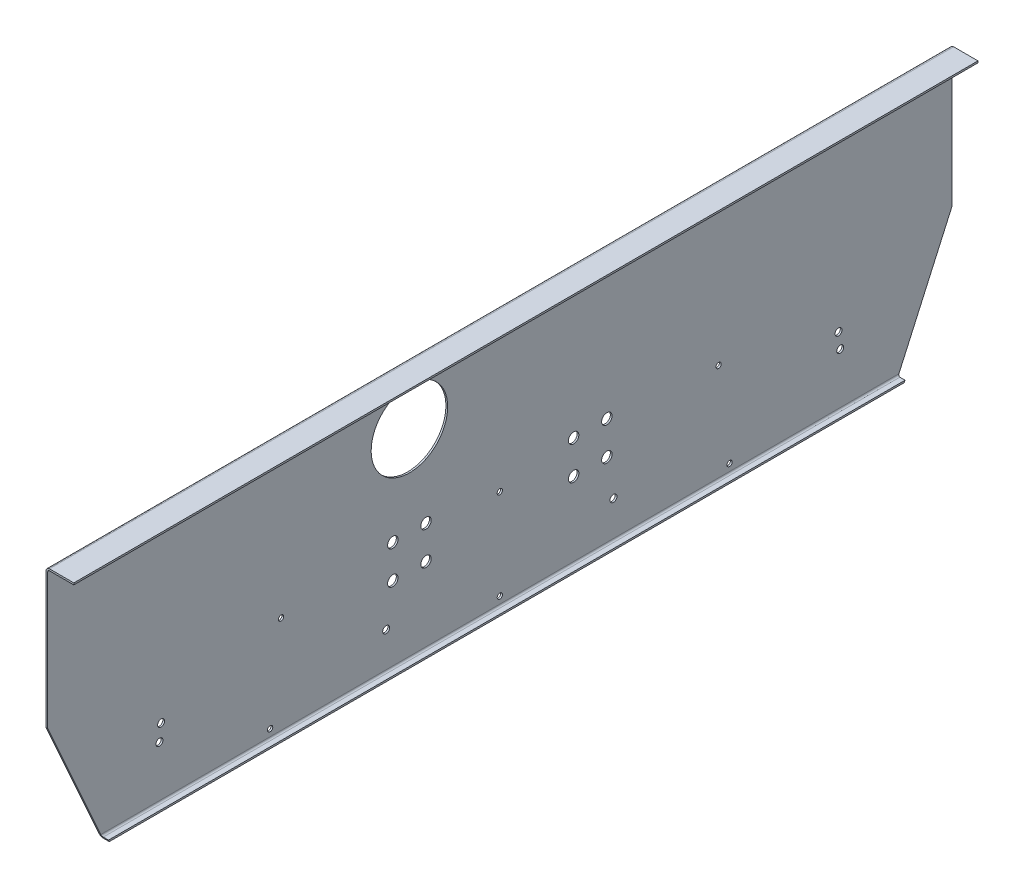
SolidWorks part; units mm, degrees
material "6061-T6 (SS)"
ref_plane "Front Plane" through (0, 0, 0) normal (0, 0, 1) x (1, 0, 0)
ref_plane "Top Plane" through (0, 0, 0) normal (0, 1, 0) x (1, 0, 0)
ref_plane "Right Plane" through (0, 0, 0) normal (1, 0, 0) x (0, 0, -1)
sketch "Sketch3" plane through (0, 0, 0) normal (0, 0, 1) x (1, 0, 0)
  line L0 (3.175, 233.4895) -> (25.4, 233.4895)
  line L1 (0, 231.902) -> (0, 0)
  line L4 (1.5875, 0) -> (1.5875, 231.902)
  line L5 (25.4, 233.4895) -> (25.4, 235.077)
  line L6 (25.4, 235.077) -> (3.175, 235.077)
  line L7 (0, 115.951) -> (26.891, 115.951) construction
  line L8 (7.9375, -1.5875) -> (7.9375, -3.175)
  line L9 (3.175, -1.5875) -> (7.9375, -1.5875)
  line L10 (7.9375, -3.175) -> (3.175, -3.175)
  arc A0 (0, 231.902) -> (3.175, 235.077) centre (3.175, 231.902) cw
  arc A1 (1.5875, 231.902) -> (3.175, 233.4895) centre (3.175, 231.902) cw
  arc A2 (0, 0) -> (3.175, -3.175) centre (3.175, 0) ccw
  arc A3 (1.5875, 0) -> (3.175, -1.5875) centre (3.175, 0) ccw
  dimension "D3" = 1.5875
  dimension "D4" = 1.5875
  dimension "D1" = 1.5875
  dimension "D2" = 231.902
  dimension "D5" = 25.4
  dimension "D6" = 7.9375
base flange "Base-Flange2" sketch "Sketch3" thickness 825.5 reverse thickness direction no parameters "D1"=0.7366
sketch "Sketch1" plane through (0, 0, 0) normal (1, 0, 0) x (0, 0, -1)
  line L0 (0, 0) -> (825.5, 0) construction
  line L1 (407.3648, 6.35) -> (418.1352, 6.35) construction
  line L2 (825.5, 0) -> (825.5, 95.25) construction
  line L3 (0, 95.25) -> (825.5, 95.25) construction
  line L4 (0, 95.25) -> (0, 0) construction
  line L5 (622.4782, 0) -> (622.4782, 6.35) construction
  line L6 (-12.1207, 0) -> (-42.1566, 0) construction
  line L7 (-44.9273, -69.85) -> (939.266, -69.85) construction
  line L8 (825.5, -69.85) -> (825.5, 107.95) construction
  line L9 (308.991, 31.75) -> (516.509, 31.75) construction
  line L10 (219.9555, 31.75) -> (427.4735, 31.75) construction
  line L11 (516.509, 31.75) -> (722.0074, 60.6309) construction
  line L12 (308.991, 31.75) -> (103.4926, 60.6309) construction
  line L13 (412.75, 0) -> (412.75, 6.35) construction
  line L14 (412.75, 95.25) -> (412.75, 88.9) construction
  line L15 (612.4655, 95.25) -> (612.4655, 88.9) construction
  line L16 (614.8828, 6.35) -> (630.0737, 6.35) construction
  line L17 (600.5116, 88.9) -> (624.4194, 88.9) construction
  line L18 (203.0218, 0) -> (203.0218, 6.35) construction
  line L19 (195.4263, 6.35) -> (210.6172, 6.35) construction
  line L20 (213.0345, 95.25) -> (213.0345, 88.9) construction
  line L21 (308.991, 31.75) -> (101.9785, 46.2257) construction
  line L22 (516.509, 31.75) -> (723.5215, 46.2257) construction
  line L23 (201.0806, 88.9) -> (224.9884, 88.9) construction
  line L24 (1.8926, 60.6309) -> (386.0676, 60.6309) construction
  line L40 (386.0676, 0) -> (386.0676, 95.25) construction
  line L41 (825.5, 231.902) -> (825.5, 0) construction
  line L42 (825.5, -3.175) -> (0, -3.175) construction
  line L43 (775.673, -3.175) -> (825.5, 107.95)
  line L44 (825.5, 107.95) -> (825.5, -3.175)
  line L45 (825.5, -3.175) -> (775.673, -3.175)
  line L46 (0, 107.95) -> (0, -3.175)
  line L47 (49.827, -3.175) -> (0, 107.95)
  line L48 (0, -3.175) -> (49.827, -3.175)
  line L49 (825.5, 0) -> (825.5, 231.902) construction
  line L50 (480.1426, 67.3925) -> (510.4575, 67.3925) construction
  line L51 (480.1426, 67.3925) -> (480.1426, 97.7074) construction
  line L52 (480.1426, 97.7074) -> (510.4575, 97.7074) construction
  line L53 (510.4575, 67.3925) -> (510.4575, 97.7074) construction
  line L54 (480.1426, 67.3925) -> (510.4575, 97.7074) construction
  line L55 (480.1426, 97.7074) -> (510.4575, 67.3925) construction
  line L56 (0, 0) -> (0, 231.902) construction
  line L57 (315.0425, 67.3925) -> (345.3574, 67.3925) construction
  line L58 (315.0425, 67.3925) -> (315.0425, 97.7074) construction
  line L59 (315.0425, 97.7074) -> (345.3574, 97.7074) construction
  line L60 (345.3574, 67.3925) -> (345.3574, 97.7074) construction
  line L61 (315.0425, 67.3925) -> (345.3574, 97.7074) construction
  line L62 (315.0425, 97.7074) -> (345.3574, 67.3925) construction
  circle A0 centre (516.509, 31.75) radius 3.175
  circle A1 centre (308.991, 31.75) radius 3.175
  circle A2 centre (308.991, 31.75) radius 101.6 construction
  circle A3 centre (516.509, 31.75) radius 101.6 construction
  circle A4 centre (103.4926, 60.6309) radius 3.175
  circle A5 centre (722.0074, 60.6309) radius 3.175
  circle A6 centre (722.0074, 60.6309) radius 101.6 construction
  circle A7 centre (103.4926, 60.6309) radius 101.6 construction
  circle A8 centre (412.75, 6.35) radius 2.413
  circle A9 centre (412.75, 88.9) radius 2.413
  circle A10 centre (622.4782, 6.35) radius 2.413
  circle A11 centre (612.4655, 88.9) radius 2.413
  circle A12 centre (203.0218, 6.35) radius 2.413
  circle A13 centre (101.9785, 46.2257) radius 3.175
  circle A14 centre (101.9785, 46.2257) radius 101.6 construction
  circle A15 centre (723.5215, 46.2257) radius 3.175
  circle A16 centre (723.5215, 46.2257) radius 101.6 construction
  circle A17 centre (213.0345, 88.9) radius 2.413
  circle A18 centre (213.0345, 88.9) radius 4.7625 construction
  circle A19 centre (722.0074, 60.6309) radius 50.4825 construction
  circle A20 centre (516.509, 31.75) radius 50.4825 construction
  circle A21 centre (308.991, 31.75) radius 50.4825 construction
  circle A22 centre (103.4926, 60.6309) radius 50.4825 construction
  circle A42 centre (510.4575, 97.7074) radius 4.7625
  circle A43 centre (480.1426, 97.7074) radius 4.7625
  circle A44 centre (480.1426, 67.3925) radius 4.7625
  circle A45 centre (510.4575, 67.3925) radius 4.7625
  circle A46 centre (345.3574, 97.7074) radius 4.7625
  circle A47 centre (315.0425, 97.7074) radius 4.7625
  circle A48 centre (345.3574, 67.3925) radius 4.7625
  circle A49 centre (315.0425, 67.3925) radius 4.7625
  circle A50 centre (330.2, 179.9611) radius 34.925
  point P16 (419.9974, 0)
  point P17 (412.75, 31.75)
  point P18 (419.9974, 0)
  point P21 (412.75, 31.75)
  point P32 (516.509, 28.575)
  point P33 (516.509, 34.925)
  point P34 (722.0074, 63.8059)
  point P35 (722.0074, 57.4559)
  point P36 (405.5026, 0)
  point P43 (388.3025, 95.25)
  point P44 (437.1975, 95.25)
  point P116 (813.9966, 0)
  point P117 (801.073, -3.175)
  point P120 (775.673, -3.175)
  point P127 (495.3, 82.55)
  point P138 (330.2, 82.55)
  dimension "D3" = 207.518
  dimension "D5" = 203.2
  dimension "D4" = 6.35
  dimension "D10" = 63.5
  dimension "D15" = 4.826
  dimension "D18" = 6.35
  dimension "D21" = 4
  dimension "D22" = 101.9785
  dimension "D23" = 9.525
  dimension "D24" = 100.965
  dimension "D26" = 183.1361
  dimension "D57" = 9.525
  dimension "D28" = 69.85
  dimension "D2" = 6.35
  dimension "D6" = 8
  dimension "D7" = 8
  dimension "D8" = 30.3149
  dimension "D9" = 31.75
  dimension "D11" = 177.8
  dimension "D12" = 6.35
  dimension "D13" = 6.35
  dimension "D14" = 6.35
  dimension "D16" = 25.4
  dimension "D17" = 6.35
  dimension "D19" = 48.8951
  dimension "D20" = 4
  dimension "D25" = 384.175
  dimension "D27" = 330.2
  dimension "D55" = 85.725
  dimension "D56" = 330.2
  dimension "D58" = 85.725
  dimension "D59" = 330.2
sketch "Bend-Lines3" plane through (0, 0, 0) normal (0, 1, 0) x (1, 0, 0)
sketch "Bounding-Box3" plane through (0, 0, 0) normal (0, 1, 0) x (1, 0, 0)
extrude "Cut-Extrude3" cut sketch "Sketch1" along normal through all normal cut yes
sheet metal parameters "Sheet-Metal3" thickness 825.5 parameters "D1"=0.7366, "D7"=685.8
flat pattern "Flat-Pattern3"
sketch "Bend-Lines4" plane through (0, 0, 0) normal (0, 1, 0) x (1, 0, 0)
sketch3d "Bounding-Box4"
  line L0 (4.7361, -3.5327, 0) -> (22.3415, 235.0684, 0) construction
  line L1 (-20.4181, -1.6767, 0) -> (-2.8127, 236.9244, 0) construction
  line L2 (4.7361, -3.5327, 0) -> (-20.4181, -1.6767, 0) construction
  line L3 (22.3415, 235.0684, 0) -> (-2.8127, 236.9244, 0) construction
